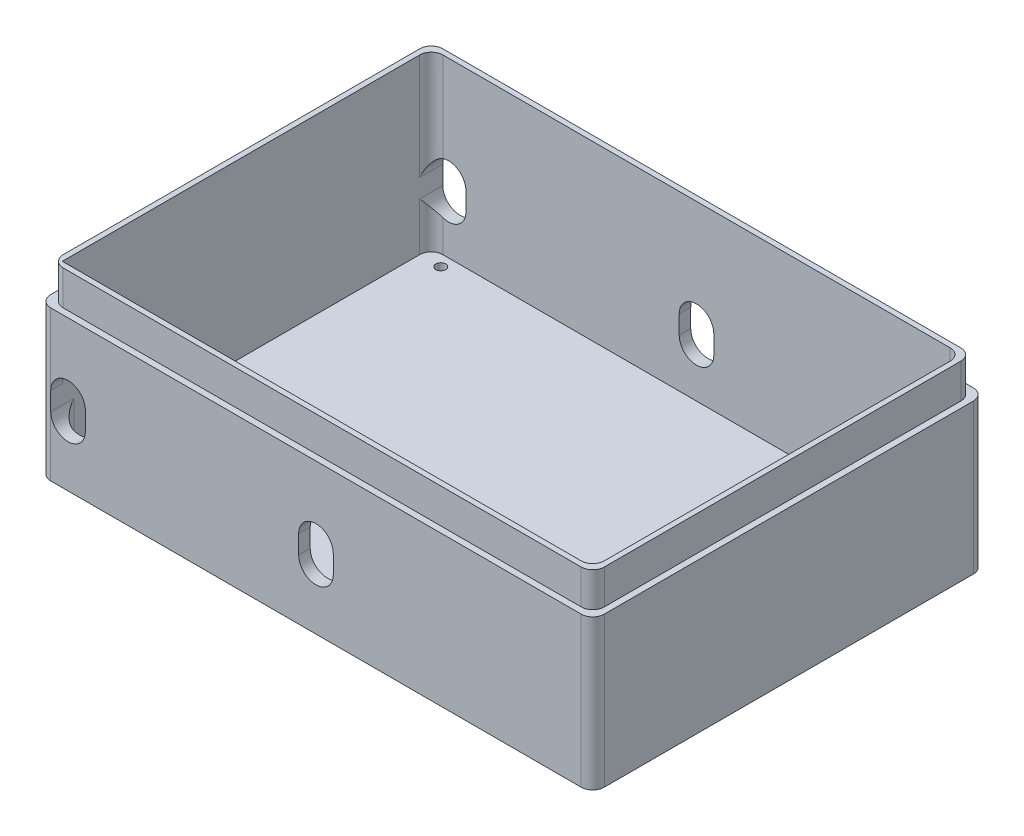
SolidWorks part; units mm, degrees
ref_plane "前视基准面" through (0, 0, 0) normal (0, 0, 1) x (1, 0, 0)
ref_plane "上视基准面" through (0, 0, 0) normal (0, 1, 0) x (1, 0, 0)
ref_plane "右视基准面" through (0, 0, 0) normal (1, 0, 0) x (0, 0, -1)
other "Configuration Table"
sketch "草图1" plane through (0, 0, 0) normal (0, 1, 0) x (1, 0, 0)
  line L1 (-120, 85) -> (120, 85)
  line L2 (-120, 85) -> (-120, -85)
  line L3 (-120, -85) -> (120, -85)
  line L4 (120, 85) -> (120, -85)
  line L5 (-120, 85) -> (120, -85) construction
  line L6 (-120, -85) -> (120, 85) construction
  line L7 (-105.8824, 75) -> (105.8824, 75) construction
  line L8 (-105.8824, 75) -> (-105.8824, -75) construction
  line L9 (-105.8824, -75) -> (105.8824, -75) construction
  line L10 (105.8824, 75) -> (105.8824, -75) construction
  line L11 (-105.8824, 75) -> (105.8824, -75) construction
  line L12 (-105.8824, -75) -> (105.8824, 75) construction
  circle A0 centre (-105.8824, 75) radius 2.15
  circle A1 centre (105.8824, 75) radius 2.15
  circle A2 centre (105.8824, -75) radius 2.15
  circle A3 centre (-105.8824, -75) radius 2.15
  point P0 (0, 0)
  point P6 (0, 0)
  dimension "D4" = 4.3
  dimension "D1" = 170
  dimension "D2" = 240
  dimension "D3" = 150
extrude "凸台-拉伸1" add sketch "草图1" along normal blind 80
sketch "草图2" plane through (0, 80, 0) normal (0, 1, 0) x (1, 0, 0)
  line L0 (-120, 85) -> (-120, -85) construction
  line L1 (115, -80) -> (-115, -80)
  line L2 (115, -80) -> (115, 80)
  line L3 (115, 80) -> (-115, 80)
  line L4 (-115, -80) -> (-115, 80)
  line L5 (115, -80) -> (-115, 80) construction
  line L6 (115, 80) -> (-115, -80) construction
  line L7 (120, 85) -> (-120, 85) construction
  point P0 (0, 0)
  dimension "D1" = 5
  dimension "D2" = 5
extrude "切除-拉伸1" cut sketch "草图2" against normal offset from surface (75 mm away) 5 up to face at (0, 0, 0)
sketch "草图9" plane through (0, 0, -80) normal (0, 0, 1) x (1, 0, 0)
  line L0 (-107.5, 26) -> (-107.5, 34) construction
  line L1 (-115, 26) -> (-115, 34)
  line L2 (-100, 26) -> (-100, 34)
  line L3 (-115, 5) -> (115, 5) construction
  line L5 (-115, 5) -> (-115, 80) construction
  line L6 (0, 26) -> (0, 34) construction
  line L7 (-7.5, 26) -> (-7.5, 34)
  line L8 (7.5, 26) -> (7.5, 34)
  line L9 (0, 5) -> (0, 55.9736) construction
  line L10 (-115, 5) -> (115, 5) construction
  arc A0 (-115, 26) -> (-100, 26) centre (-107.5, 26) ccw
  arc A1 (-100, 34) -> (-115, 34) centre (-107.5, 34) ccw
  arc A2 (-7.5, 26) -> (7.5, 26) centre (0, 26) ccw
  arc A3 (7.5, 34) -> (-7.5, 34) centre (0, 34) ccw
  point P2 (-107.5, 30)
  point P7 (-107.5, 41.5)
  point P8 (-107.5, 18.5)
  point P15 (0, 30)
  dimension "D1" = 15
  dimension "D2" = 23
  dimension "D3" = 25
extrude "切除-拉伸3" cut sketch "草图9" against normal through all both and the other way through all
fillet "圆角1" radius 5 9 edges at (-120, 40, -85) (120, 40, -85) (120, 40, 85) (-120, 40, 85) (-115, 15.5, 80) (115, 42.5, 80) (115, 42.5, -80) (-115, 15.5, -80) (-115, 57, -80)
sketch "草图12" plane through (0, 80, 0) normal (0, 1, 0) x (1, 0, 0)
  line L1 (112.3, -82.3) -> (-112.3, -82.3)
  line L2 (117.3, -77.3) -> (117.3, 77.3)
  line L3 (112.3, 82.3) -> (-112.3, 82.3)
  line L4 (-117.3, -77.3) -> (-117.3, 77.3)
  line L5 (117.3, -82.3) -> (-117.3, 82.3) construction
  line L6 (117.3, 82.3) -> (-117.3, -82.3) construction
  line L7 (115, 85) -> (-115, 85) construction
  line L8 (-120, 80) -> (-120, -80) construction
  line L10 (122.3, -87.3) -> (-122.3, -87.3)
  line L11 (122.3, -87.3) -> (122.3, 87.3)
  line L12 (122.3, 87.3) -> (-122.3, 87.3)
  line L13 (-122.3, -87.3) -> (-122.3, 87.3)
  line L14 (122.3, -87.3) -> (-122.3, 87.3) construction
  line L15 (122.3, 87.3) -> (-122.3, -87.3) construction
  arc A0 (-112.3, -82.3) -> (-117.3, -77.3) centre (-112.3, -77.3) cw
  arc A1 (112.3, -82.3) -> (117.3, -77.3) centre (112.3, -77.3) ccw
  arc A2 (117.3, 77.3) -> (112.3, 82.3) centre (112.3, 77.3) ccw
  arc A3 (-112.3, 82.3) -> (-117.3, 77.3) centre (-112.3, 77.3) ccw
  point P21 (0, 0)
  line M20 (115, 85) -> (-115, 85)
  arc M21 (-115, 85) -> (-120, 80) centre (-115, 80) ccw
  line M22 (-120, 80) -> (-120, -80)
  arc M23 (-120, -80) -> (-115, -85) centre (-115, -80) ccw
  line M24 (-115, -85) -> (115, -85)
  arc M25 (115, -85) -> (120, -80) centre (115, -80) ccw
  line M26 (120, -80) -> (120, 80)
  arc M27 (120, 80) -> (115, 85) centre (115, 80) ccw
  dimension "D3" = 5
  dimension "D1" = 2.7
  dimension "D2" = 2.7
  dimension "D4" = 5
  dimension "D5" = 5
extrude "切除-拉伸5" cut sketch "草图12" against normal blind 15 contours L13 L10 L11 L12 M20 M27 M26 M25 M24 M23 M22 M21 | A3 L3 A2 L2 A1 L1 A0 L4 M27 M20 M21 M22 M23 M24 M25 M26
